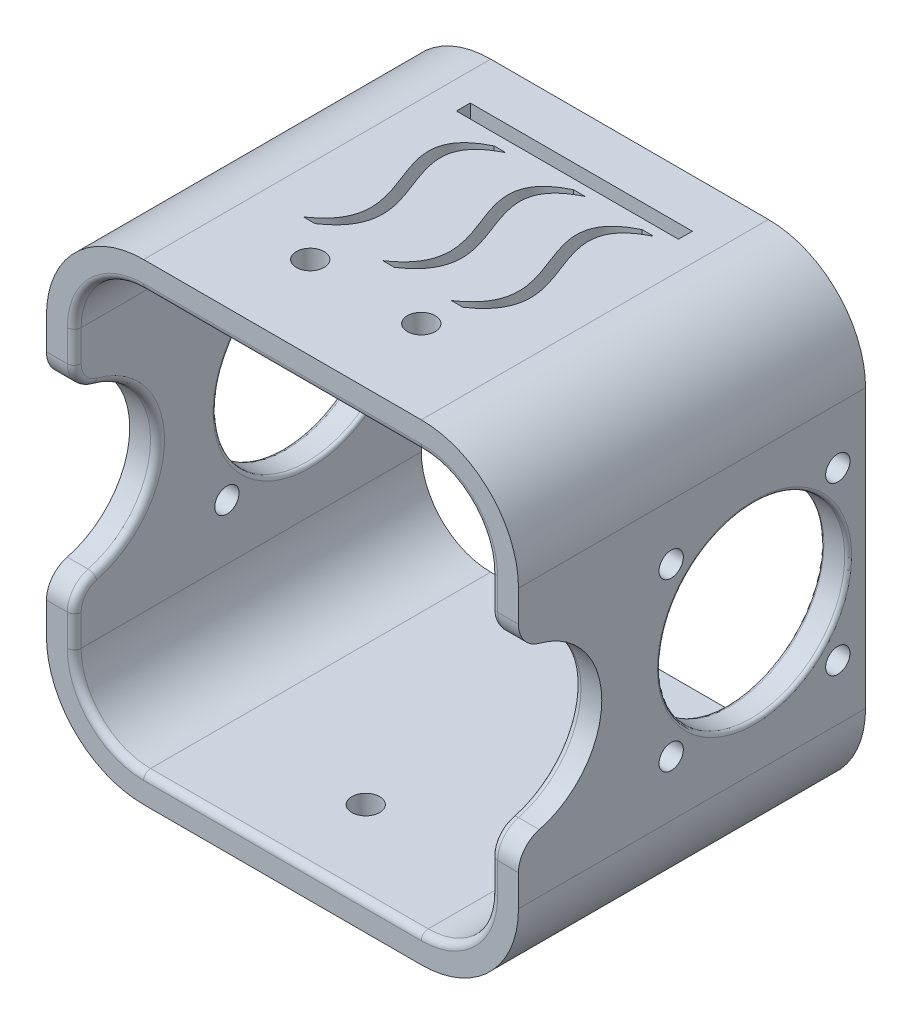
SolidWorks part; units mm, degrees
ref_plane "Piano frontale" through (0, 0, 0) normal (0, 0, 1) x (1, 0, 0)
ref_plane "Piano superiore" through (0, 0, 0) normal (0, 1, 0) x (1, 0, 0)
ref_plane "Piano destro" through (0, 0, 0) normal (1, 0, 0) x (0, 0, -1)
sketch "Schizzo1" plane through (0, 0, 0) normal (0, 0, 1) x (1, 0, 0)
  line L0 (-10, 0) -> (-50, 0)
  line L1 (0, -10) -> (0, -50)
  line L2 (-60, -10) -> (-60, -50)
  line L3 (-50, -60) -> (-10, -60)
  arc A0 (0, -50) -> (-10, -60) centre (-10, -50) cw
  arc A1 (-50, -60) -> (-60, -50) centre (-50, -50) cw
  arc A2 (0, -10) -> (-10, 0) centre (-10, -10) ccw
  arc A3 (-60, -10) -> (-50, 0) centre (-50, -10) cw
  point P7 (0, -60)
  point P10 (-60, -60)
  point P13 (0, 0)
  point P16 (-60, 0)
  dimension "D4" = 10
  dimension "D1" = 60
  dimension "D2" = 60
  dimension "D3" = 60
extrude "Estrusione-Sottile1" add sketch "Schizzo1" along normal blind 50 thin thin type one direction wall 4
sketch "Schizzo2" plane through (0, 4, 0) normal (0, 1, 0) x (1, 0, 0)
  line L0 (-30, 0) -> (-30, -50) construction
  line L1 (-10, 0) -> (-50, 0) construction
  line L2 (-10, -50) -> (-50, -50) construction
  circle A0 centre (-38, -38) radius 2
  circle A1 centre (-22, -38) radius 2
  dimension "D5" = 4
  dimension "D6" = 4
  dimension "D1" = 8
  dimension "D2" = 8
  dimension "D3" = 12
  dimension "D4" = 12
extrude "Taglio-Estrusione1" cut sketch "Schizzo2" against normal blind 10
sketch "Schizzo3" plane through (-64, 0, 0) normal (-1, 0, 0) x (0, 0, 1)
  line L0 (50, -10) -> (50, -50) construction
  circle A0 centre (50, -30) radius 12
  dimension "D1" = 24
extrude "Taglio-Estrusione2" cut sketch "Schizzo3" along direction (-1, 0, 0) on the side against the normal up to surface (68 mm away) up to face at (4, -30, 25)
fillet "Raccordo1" radius 4 1 edges at (-62, -18, 50) type face fillet first side face at (-30, -7.8382, 50) second side face at (-62, -30, 44)
fillet "Raccordo2" radius 4 1 edges at (-62, -42, 50) type face fillet first side face at (-62, -30.8513, 43.2978) second side face at (-30, -52.1618, 50)
fillet "Raccordo3" radius 4 1 edges at (2, -18, 50) type face fillet first side face at (2, -30, 44) second side face at (-30, -7.2563, 50)
fillet "Raccordo4" radius 4 1 edges at (2, -42, 50) type face fillet first side face at (2, -30.8513, 43.2978) second side face at (-30, -52.7437, 50)
sketch "Schizzo4" plane through (0, -64, 0) normal (0, -1, 0) x (1, 0, 0)
  line L0 (-30, 50) -> (-30, 0) construction
  line L1 (-50, 50) -> (-10, 50) construction
  line L2 (-50, 0) -> (-10, 0) construction
  circle A0 centre (-30, 38) radius 2
  dimension "D1" = 4
  dimension "D2" = 12
extrude "Taglio-Estrusione3" cut sketch "Schizzo4" against normal blind 10
sketch "Schizzo5" plane through (0, 4, 0) normal (0, 1, 0) x (1, 0, 0)
  line L0 (-30, 0) -> (-30, -50) construction
  line L1 (-46, -6.9458) -> (-14, -6.9458)
  line L2 (-46, -6.9458) -> (-46, -8.9458)
  line L3 (-46, -8.9458) -> (-14, -8.9458)
  line L4 (-14, -6.9458) -> (-14, -8.9458)
  line L5 (-10, 0) -> (-50, 0) construction
  line L6 (-10, -50) -> (-50, -50) construction
  line L7 (-30.9605, -32.9287) -> (-32.6391, -32.9195)
  line L8 (-26.0641, -10.3322) -> (-27.7428, -10.3231)
  line L9 (-42.1357, -33.1817) -> (-43.8144, -33.1725)
  line L10 (-37.2394, -10.5852) -> (-38.918, -10.576)
  line L11 (-21.0473, -32.9631) -> (-22.7259, -32.9539)
  line L12 (-16.1509, -10.3666) -> (-17.8296, -10.3574)
  spline S0 degree 3 poles (-16.1509, -10.3666) (-27.5731, -15.9557) (-10.2901, -25.7029) (-21.0473, -32.9631) knots 0 0 0 0 1 1 1 1
  spline S1 degree 3 poles (-17.8296, -10.3574) (-29.2518, -15.9465) (-11.9688, -25.6937) (-22.7259, -32.9539) knots 0 0 0 0 1 1 1 1
  spline S2 degree 3 poles (-26.0641, -10.3322) (-37.4863, -15.9213) (-20.2033, -25.6686) (-30.9605, -32.9287) knots 0 0 0 0 1 1 1 1
  spline S3 degree 3 poles (-27.7428, -10.3231) (-39.1649, -15.9122) (-21.882, -25.6594) (-32.6391, -32.9195) knots 0 0 0 0 1 1 1 1
  spline S4 degree 3 poles (-37.2394, -10.5852) (-48.6615, -16.1743) (-31.3786, -25.9215) (-42.1357, -33.1817) knots 0 0 0 0 1 1 1 1
  spline S5 degree 3 poles (-38.918, -10.576) (-50.3402, -16.1651) (-33.0573, -25.9123) (-43.8144, -33.1725) knots 0 0 0 0 1 1 1 1
  dimension "D1" = 16
  dimension "D2" = 16
  dimension "D3" = 2
extrude "Taglio-Estrusione4" cut sketch "Schizzo5" against normal blind 10
sketch "Schizzo7" plane through (-64, 0, 0) normal (-1, 0, 0) x (0, 0, 1)
  line L0 (0, -30) -> (38, -30) construction
  line L1 (0, -10) -> (0, -50) construction
  line L2 (0, -18) -> (47.951, -18) construction
  line L3 (0, -42) -> (47.951, -42) construction
  line L4 (16, -18) -> (16, -42) construction
  arc A0 (47, -18.381) -> (47, -41.619) centre (50, -30) ccw construction
  arc A1 (47, -18.381) -> (50, -14.5081) centre (46, -14.5081) ccw construction
  arc A2 (50, -45.4919) -> (47, -41.619) centre (46, -45.4919) ccw construction
  circle A3 centre (28, -18) radius 1.75
  circle A4 centre (28, -42) radius 1.75
  circle A5 centre (4, -42) radius 1.75
  circle A6 centre (4, -18) radius 1.75
  dimension "D4" = 3.5
  dimension "D1" = 12
  dimension "D2" = 12
  dimension "D3" = 16
  dimension "D5" = 12
extrude "Taglio-Estrusione5" cut sketch "Schizzo7" against normal up to surface (68 mm away) up to face at (4, -30, 35.7906)
sketch "Schizzo8" plane through (-64, 0, 0) normal (-1, 0, 0) x (0, 0, 1)
  circle A0 centre (16, -30) radius 13.5
  dimension "D1" = 27
extrude "Taglio-Estrusione6" cut sketch "Schizzo8" against normal up to surface (68 mm away) up to face at (4, -19.75, 4)
fillet "Raccordo5" radius 0.5 1 edges at (-64, -43.5, 16) type face fillet first side face at (-64, -43.5, 16) second side face at (-60, -16.5, 16)
fillet "Raccordo6" radius 0.5 1 edges at (-60, -16.5, 16) type face fillet first side face at (-60, -16.5, 16) second side face at (-63.5, -16.5, 16)
fillet "Raccordo7" radius 0.5 1 edges at (4, -43.5, 16) type face fillet first side face at (4, -43.5, 16) second side face at (0, -43.5, 16)
fillet "Raccordo8" radius 0.5 1 edges at (0, -43.5, 16) type face fillet first side face at (0, -43.5, 16) second side face at (3.5, -43.5, 16)
fillet "Raccordo9" radius 1 1 edges at (-57.0711, -2.9289, 50) type face fillet first side face at (-30, -6.6743, 50) second side face at (-56.0355, -3.9645, 25)
